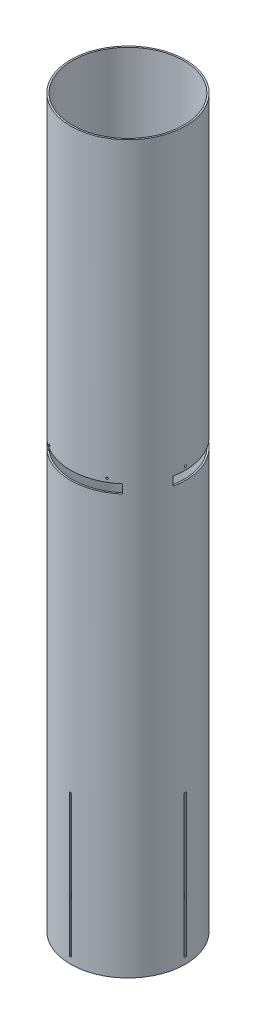
SolidWorks part; units mm, degrees
material "A-Glass Fiber"
ref_plane "Front Plane" through (0, 0, 0) normal (0, 0, 1) x (1, 0, 0)
ref_plane "Top Plane" through (0, 0, 0) normal (0, 1, 0) x (1, 0, 0)
ref_plane "Right Plane" through (0, 0, 0) normal (1, 0, 0) x (0, 0, -1)
sketch "Sketch1" plane through (0, 0, 0) normal (0, 1, 0) x (1, 0, 0)
  circle A0 centre (0, 0) radius 76.2
  circle A1 centre (0, 0) radius 78.359
  dimension "D1" = 152.4
  dimension "D2" = 156.718
extrude "Boss-Extrude1" add sketch "Sketch1" along normal blind 990.6
ref_plane "Plane1" through (0, 0, 0) normal (0.7071, 0, 0.7071) x (0.7071, 0, -0.7071)
ref_axis "Axis1" through (0, 990.6, 0) along (0, -1, 0)
sketch "Sketch2" plane through (0, 0, 0) normal (1, 0, 0) x (0, 0, -1)
  line L0 (0, 0) -> (0, 8.89)
  line L1 (1.5875, 8.89) -> (-1.5875, 8.89)
  line L2 (1.5875, 8.89) -> (1.5875, 203.2)
  line L3 (1.5875, 203.2) -> (-1.5875, 203.2)
  line L4 (-1.5875, 8.89) -> (-1.5875, 203.2)
  line L5 (1.5875, 8.89) -> (-1.5875, 203.2) construction
  line L6 (1.5875, 203.2) -> (-1.5875, 8.89) construction
  line L7 (78.359, 990.6) -> (-78.359, 990.6) construction
  line L8 (78.359, 990.6) -> (-78.359, 990.6)
  line L9 (0, 990.6) -> (0, 588.645)
  line L10 (-78.359, 0) -> (78.359, 0) construction
  circle A0 centre (0, 588.645) radius 1.3525
  point P0 (0, 106.045)
  dimension "D4" = 2.7051
  dimension "D1" = 3.175
  dimension "D2" = 194.31
  dimension "D5" = 588.645
  dimension "D3" = 203.2
extrude "Cut-Extrude1" cut sketch "Sketch2" against normal through all contours L4 L1 L2 L3 region at (0, 106.045, 0)
pattern_circular "CirPattern1" count 4 over 360 about axis through (0, 0, 0) along (0, 1, 0) of "Cut-Extrude1" reverse direction yes
extrude "Cut-Extrude2" cut sketch "Sketch2<3>" against normal through all contours A0 region at (0, 587.7157, 0.9293)
sketch "Sketch2<3>" plane through (0, 0, 0) normal (1, 0, 0) x (0, 0, -1) same geometry as "Sketch2"
pattern_circular "CirPattern2" count 6 over 360 about axis through (0, 990.6, 0) along (0, -1, 0) of "Cut-Extrude2"
sketch "Sketch3" plane through (0, 0, 0) normal (0.7071, 0, 0.7071) x (0.7071, 0, -0.7071)
  line L0 (0, 0) -> (0, 127) construction
  circle A0 centre (0, 127) radius 3.175
  dimension "D1" = 6.35
  dimension "D2" = 127
extrude "Cut-Extrude3" cut sketch "Sketch3" against normal through all
ref_plane "Plane3" through (0, 583.8825, 0) normal (0, 1, 0) x (1, 0, 0)
sketch "Sketch7" plane through (0, 583.8825, 0) normal (0, 1, 0) x (1, 0, 0)
  line L0 (0, 0) -> (-76.8534, -15.2871)
  line L1 (0, 0) -> (0, 93.232) construction
  line L2 (0, 0) -> (-25.1877, 74.2005)
  line L3 (-78.359, 0) -> (0, 0) construction
  arc A0 (-78.3473, 1.3526) -> (-78.3473, -1.3525) centre (0, 0) ccw construction
  circle A1 centre (0, 0) radius 76.2 construction
  circle A2 centre (0, 0) radius 78.359
  circle A3 centre (0, 0) radius 78.359
  circle A4 centre (0, 0) radius 76.2
  circle A5 centre (0, 0) radius 78.359 construction
  arc A6 (-38.0023, 68.527) -> (-40.345, 67.1745) centre (0, 0) ccw construction
  arc A7 (-78.3473, 1.3526) -> (-78.3473, -1.3525) centre (0, 0) ccw
  arc A8 (-38.0023, 68.527) -> (-40.345, 67.1745) centre (0, 0) ccw
  dimension "D1" = 82.5
  dimension "D3" = 11.25
  dimension "D2" = 0
extrude "Cut-Extrude4" cut sketch "Sketch7" against normal blind 12.065 contours A4 A3 L0 region at (-75.9984, 583.8825, 14.0521)
pattern_circular "CirPattern3" count 3 over 360 about axis through (0, 990.6, 0) along (0, -1, 0) of "Cut-Extrude4"
equation "\"D1@Boss-Extrude1\" = \"Aft_Section_Length\""
equation "\"AB_Coupler_OD_Length\"= 1in"
equation "\"AB_Coupling_Section_Length\"= 0.375in"
equation "\"AB_Coupler_Length\"= \"AB_Coupler_OD_Length\" + \"AB_Coupling_Section_Length\" * 2"
equation "\"AB_Coupler_Num_Screws\"= 6"
equation "\"AB_Coupling_Screw_Diameter\"= 0.1065in"
equation "\"Aft_Section_Length\"= 39in"
equation "\"D4@Sketch2\"=\"AB_Coupling_Screw_Diameter\""
equation "\"D1@CirPattern2\"=\"AB_Coupler_Num_Screws\""
equation "\"Rail_Nut_From_Bottom\"= 5in"
equation "\"Rail_Nut_Diam\"= 0.25in"
equation "\"D1@Sketch3\"=\"Rail_Nut_Diam\""
equation "\"D2@Sketch3\"=\"Rail_Nut_From_Bottom\""
equation "\"AB_BKHD_Thickness\" = 0.375in"
equation "\"AB_Mount_From_Bottom\" = 23.175in"
equation "\"Cutout_Angle\" =80"
